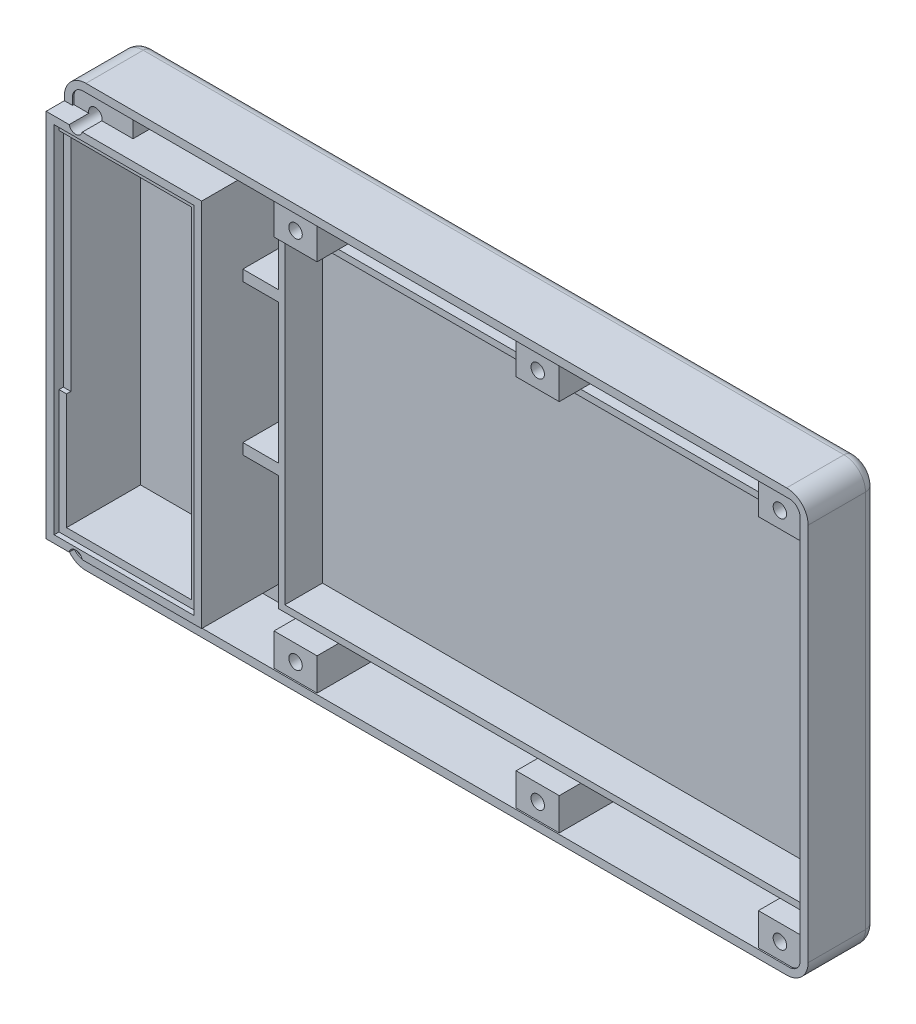
SolidWorks part; units mm, degrees
ref_plane "Plan de face" through (0, 0, 0) normal (0, 0, 1) x (1, 0, 0)
ref_plane "Plan de dessus" through (0, 0, 0) normal (0, 1, 0) x (1, 0, 0)
ref_plane "Plan de droite" through (0, 0, 0) normal (1, 0, 0) x (0, 0, -1)
sketch "Esquisse1" plane through (0, 0, 0) normal (0, 0, 1) x (1, 0, 0)
  line L0 (135.2, 69.4) -> (34, 69.4)
  line L1 (0, 0) -> (133.2, 0)
  line L2 (0, 0) -> (0, 75.4)
  line L3 (0, 75.4) -> (133.2, 75.4)
  line L4 (135.2, 2) -> (135.2, 73.4)
  line L5 (34, 69.4) -> (34, 6)
  line L6 (34, 6) -> (135.2, 6)
  line L7 (135.2, 68.2) -> (35.2, 68.2)
  line L8 (35.2, 68.2) -> (35.2, 7.2)
  line L9 (35.2, 7.2) -> (135.2, 7.2)
  line L10 (-19.055, 37.7) -> (204.5006, 37.7) construction
  line L11 (-1.5, 76.9) -> (136.7, 76.9)
  line L12 (-1.5, 76.9) -> (-1.5, -1.5)
  line L13 (-1.5, -1.5) -> (136.7, -1.5)
  line L14 (136.7, 76.9) -> (136.7, -1.5)
  line L15 (0, 72.1) -> (0, 70.7)
  line L16 (26, 70.7) -> (0, 70.7)
  line L17 (26, 70.7) -> (26, 4.7)
  line L18 (26, 4.7) -> (0, 4.7)
  line L19 (0, 70.7) -> (0, 4.7)
  line L20 (1.4, 69.3) -> (24.6, 69.3)
  line L21 (1.4, 69.3) -> (1.4, 6.1)
  line L22 (1.4, 6.1) -> (24.6, 6.1)
  line L23 (24.6, 69.3) -> (24.6, 6.1)
  line L24 (0, 72.1) -> (27.4, 72.1)
  line L25 (0, 3.3) -> (0, 4.7)
  line L26 (0, 3.3) -> (27.4, 3.3)
  line L27 (27.4, 72.1) -> (27.4, 3.3)
  line L28 (127.2, 75.4) -> (127.2, 69.4)
  line L30 (82.2, 75.4) -> (82.2, 69.4)
  line L31 (90.2, 75.4) -> (90.2, 69.4)
  line L32 (37.2, 75.4) -> (37.2, 69.4)
  line L33 (45.2, 75.4) -> (45.2, 69.4)
  line L35 (127.2, 0) -> (127.2, 6)
  line L36 (90.2, 0) -> (90.2, 6)
  line L37 (82.2, 0) -> (82.2, 6)
  line L38 (45.2, 0) -> (45.2, 6)
  line L39 (37.2, 0) -> (37.2, 6)
  circle A0 centre (131.2, 72.4) radius 1.25
  arc A1 (133.2, 75.4) -> (135.2, 73.4) centre (133.2, 73.4) cw
  arc A2 (133.2, 0) -> (135.2, 2) centre (133.2, 2) ccw
  circle A3 centre (86.2, 72.4) radius 1.25
  circle A5 centre (41.2, 72.4) radius 1.25
  circle A6 centre (131.2, 3) radius 1.25
  circle A8 centre (86.2, 3) radius 1.25
  circle A11 centre (41.2, 3) radius 1.25
  dimension "D12" = 2.5
  dimension "D13" = 6
  dimension "D40" = 2
  dimension "D1" = 1.5
  dimension "D3" = 1.2
  dimension "D4" = 1.2
  dimension "D5" = 1.2
  dimension "D6" = 61
  dimension "D7" = 6
  dimension "D8" = 100
  dimension "D9" = 1.5
  dimension "D10" = 1.5
  dimension "D11" = 1.5
  dimension "D15" = 30.5
  dimension "D16" = 30.5
  dimension "D17" = 3
  dimension "D18" = 66
  dimension "D19" = 26
  dimension "D20" = 33
  dimension "D21" = 33
  dimension "D22" = 8
  dimension "D23" = 1.4
  dimension "D24" = 1.4
  dimension "D25" = 1.4
  dimension "D26" = 1.4
  dimension "D27" = 1.4
  dimension "D28" = 0
  dimension "D29" = 1.4
  dimension "D30" = 1.4
  dimension "D31" = 4
  dimension "D32" = 0
  dimension "D33" = 0
  dimension "D34" = 4
  dimension "D35" = 45
  dimension "D36" = 4
  dimension "D37" = 4
  dimension "D38" = 4
  dimension "D39" = 4
  dimension "D14" = 3
extrude "Boss.-Extru.1" add sketch "Esquisse1" along normal blind 12.65 contours L12 L10 L2 L3 L4 L14 L11 | L10 L12 L13 L14 L4 L1 L2 region at (136.6365, 71.4, 0) region at (135.95, 36.2635, 0)
extrude "Boss.-Extru.2" add sketch "Esquisse1<4>" along normal blind 1.4 contours L3 A1 L4 A2 L1 L2
sketch "Esquisse1<4>" plane through (0, 0, 0) normal (0, 0, 1) x (1, 0, 0) same geometry as "Esquisse1"
extrude "Boss.-Extru.5" add sketch "Esquisse1<5>" along normal blind 11 from surface separate body contours A5 | A3 | A0 | A11 | A8 | A6 region at (131.2, 69.5, 0) region at (86.2, 69.5, 0) region at (135.1, 4, 0) region at (41.2, 69.5, 0) region at (90.1, 3, 0) region at (45.1, 3, 0) starting at face at (89.6047, 37.7, 1.4)
sketch "Esquisse1<5>" plane through (0, 0, 0) normal (0, 0, 1) x (1, 0, 0) same geometry as "Esquisse1"
extrude "Boss.-Extru.7" add sketch "Esquisse1<6>" along normal blind 7 from surface contours L5 L10 L8 L7 L4 L0 | L10 L5 L6 L4 L9 L8 region at (134.1395, 68.8, 0) region at (134.1395, 6.6, 0) starting at face at (89.6047, 37.7, 1.4)
sketch "Esquisse1<6>" plane through (0, 0, 0) normal (0, 0, 1) x (1, 0, 0) same geometry as "Esquisse1"
fillet "Congé1" radius 4 4 edges at (-1.5, 76.9, 6.325) (-1.5, -1.5, 6.325) (136.7, -1.5, 6.325) (136.7, 76.9, 6.325)
fillet "Congé4" radius 2 2 edges at (0, 0, 7.025) (0, 75.4, 7.025)
extrude "Boss.-Extru.8" add sketch "Esquisse1<7>" along normal blind 13.75 from surface contours L19 L10 L21 L20 L23 L17 L16 | L10 L19 L18 L17 L23 L22 L21 region at (25.5799, 21.2, 0) region at (25.3, 38.1201, 0) starting at face at (73.2667, 37.7, 1.4)
sketch "Esquisse1<7>" plane through (0, 0, 0) normal (0, 0, 1) x (1, 0, 0) same geometry as "Esquisse1"
extrude "Boss.-Extru.9" add sketch "Esquisse1<8>" along normal blind 14.65 from surface contours L10 L26 L27 L17 L18 L19 | L10 L19 L16 L17 L27 L24 region at (26.9602, 20.5, 0) region at (26.7, 38.1398, 0) starting at face at (58.2, 37.7, 1.4)
sketch "Esquisse1<8>" plane through (0, 0, 0) normal (0, 0, 1) x (1, 0, 0) same geometry as "Esquisse1"
sketch "Esquisse2" plane through (0, 0, 12.65) normal (0, 0, 1) x (1, 0, 0)
  line L0 (-1.5, 72.9) -> (-1.5, 2.5) construction
  line L1 (0, 72.1) -> (-1.5, 72.1)
  line L2 (0, 72.1) -> (0, 3.3)
  line L3 (0, 3.3) -> (-1.5, 3.3)
  line L4 (-1.5, 72.1) -> (-1.5, 3.3)
  line L5 (0, 3.3) -> (27.4, 3.3) construction
  dimension "D1" = 0
sketch "Esquisse4" plane through (0, 0, 1.4) normal (0, 0, 1) x (1, 0, 0)
  line L1 (2, 0) -> (133.2, 0) construction
  line L2 (2, 75.4) -> (133.2, 75.4) construction
  line L5 (11, 75.4) -> (2, 75.4)
  line L6 (11, 75.4) -> (11, 70.7374)
  line L7 (11, 70.7374) -> (0, 70.7374)
  line L8 (0, 73.4) -> (0, 70.7374)
  line L9 (0, 4.6081) -> (11, 4.6081)
  line L10 (0, 4.6081) -> (0, 2)
  line L11 (2, 0) -> (11, 0)
  line L12 (11, 4.6081) -> (11, 0)
  circle A0 centre (4, 3) radius 1.25
  circle A1 centre (4, 72.4) radius 1.25
  circle A2 centre (41.2, 3) radius 1.25 construction
  circle A3 centre (41.2, 72.4) radius 1.25 construction
  arc A4 (0, 2) -> (2, 0) centre (2, 2) ccw
  arc A5 (2, 75.4) -> (0, 73.4) centre (2, 73.4) ccw
  line M1 (27.4, 3.3) -> (0, 3.3)
  line M11 (0, 72.1) -> (27.4, 72.1)
  dimension "D1" = 2.5
  dimension "D4" = 2.5
  dimension "D9" = 2
  dimension "D2" = 7
  dimension "D3" = 0
  dimension "D5" = 0
  dimension "D6" = 7
  dimension "D7" = 11
  dimension "D8" = 11
extrude "Boss.-Extru.11" add sketch "Esquisse4" along normal blind 11
sketch "Esquisse5" plane through (0, 0, 1.4) normal (0, 0, 1) x (1, 0, 0)
  line L16 (34, 69.4) -> (34, 6) construction
  line L21 (34, 57.3296) -> (27.4, 57.3296)
  line L22 (34, 57.3296) -> (34, 55.3296)
  line L23 (34, 55.3296) -> (27.4, 55.3296)
  line L24 (27.4, 57.3296) -> (27.4, 55.3296)
  line L25 (27.4, 72.1) -> (27.4, 3.3) construction
  line L26 (27.4, 72.1) -> (27.4, 3.3) construction
  line L27 (34, 29.422) -> (27.4, 29.422)
  line L28 (34, 29.422) -> (34, 27.422)
  line L29 (34, 27.422) -> (27.4, 27.422)
  line L30 (27.4, 29.422) -> (27.4, 27.422)
  dimension "D3" = 2
  dimension "D4" = 2
extrude "Boss.-Extru.12" add sketch "Esquisse5" along normal blind 7
fillet "Congé3" radius 2 8 edges at (-0.3284, -0.3284, 0) (-1.5, 37.7, 0) (-0.3284, 75.7284, 0) (67.6, 76.9, 0) (135.5284, 75.7284, 0) (136.7, 37.7, 0) (135.5284, -0.3284, 0) (67.6, -1.5, 0)
sketch "Esquisse7" plane through (0, 0, 15.15) normal (0, 0, 1) x (1, 0, 0)
  line L0 (0, 4.7) -> (0, 70.7) construction
  line L1 (1.4, 69.3) -> (0, 69.3)
  line L2 (1.4, 69.3) -> (1.4, 27.6196)
  line L3 (1.4, 27.6196) -> (0, 27.6196)
  line L4 (0, 69.3) -> (0, 27.6196)
extrude "Enlèv. mat.-Extru.3" cut sketch "Esquisse7" against normal blind 0.8
extrude "Boss.-Extru.14" add sketch "Esquisse2" along normal blind 3.4
extrude "Enlèv. mat.-Extru.4" cut sketch "Esquisse4<2>" along normal blind 30.15 contours A1 M11 | A1 M11 | A0 M1 | A0 M1 region at (4, 72.7726, 1.4) region at (4, 71.704, 1.4) region at (4, 2.6274, 1.4) region at (4, 3.696, 1.4)
sketch "Esquisse4<2>" plane through (0, 0, 1.4) normal (0, 0, 1) x (1, 0, 0) same geometry as "Esquisse4"
